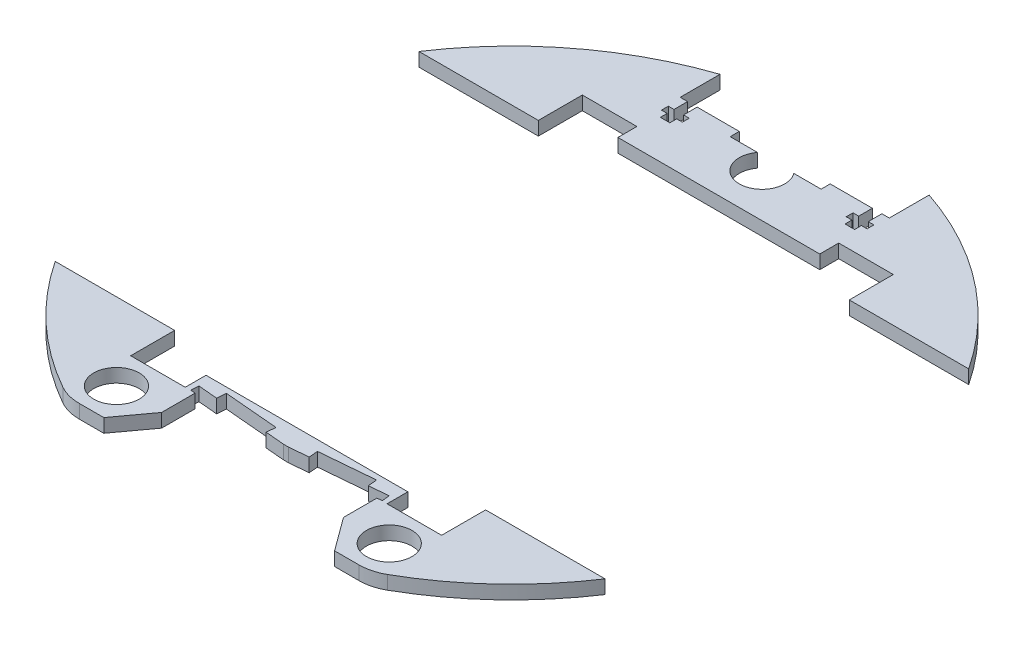
SolidWorks part; units mm, degrees
ref_plane "Front Plane" through (0, 0, 0) normal (0, 0, 1) x (1, 0, 0)
ref_plane "Top Plane" through (0, 0, 0) normal (0, 1, 0) x (1, 0, 0)
ref_plane "Right Plane" through (0, 0, 0) normal (1, 0, 0) x (0, 0, -1)
sketch "Sketch1" plane through (0, 0, 0) normal (0, 1, 0) x (1, 0, 0)
  line L0 (-30.7634, -64.4046) -> (30.7634, -64.4046)
  line L1 (0, -83.2398) -> (0, 0) construction
  line L2 (0, -83.2398) -> (33.2911, -64.4046) construction
  arc A0 (35.6856, -63.1093) -> (-35.6856, -63.1093) centre (0, 0) ccw
  circle A1 centre (0, -83.2398) radius 38.25 construction
  arc A2 (30.7634, -64.4046) -> (35.6856, -63.1093) centre (30.7634, -54.4046) ccw
  arc A3 (-30.7634, -64.4046) -> (-35.6856, -63.1093) centre (-30.7634, -54.4046) cw
  dimension "D1" = 145
  dimension "D2" = 76.5
  dimension "D4" = 10
  dimension "D3" = 60.5
extrude "Boss-Extrude1" add sketch "Sketch1" along normal blind 3
sketch "Sketch2" plane through (0, 3, 0) normal (0, 1, 0) x (1, 0, 0)
  line L5 (22.2, -49.6757) -> (22.2, -45.1)
  line L6 (22.2, -45.1) -> (-22.2, -45.1)
  line L7 (-22.2, -45.1) -> (-22.2, -49.6757)
  line L8 (22.2, 49.6757) -> (22.2, 45.5)
  line L9 (-34.2, -49.6757) -> (-22.2, -49.6757) construction
  line L10 (-34.2, -49.6757) -> (-34.2, 49.6757) construction
  line L11 (-34.2, 49.6757) -> (-22.2, 49.6757) construction
  line L19 (34.2, 49.6757) -> (22.2, 49.6757) construction
  line L20 (34.2, -49.6757) -> (34.2, 49.6757) construction
  line L21 (34.2, -49.6757) -> (22.2, -49.6757) construction
  line L22 (22.2, 45.5) -> (-22.2, 45.5)
  line L23 (-22.2, 45.5) -> (-22.2, 49.6757)
  line L35 (-34.2, -49.6757) -> (-22.2, -49.6757)
  line L36 (-34.2, -49.6757) -> (-34.2, 49.6757)
  line L37 (-34.2, 49.6757) -> (-22.2, 49.6757)
  line L55 (34.2, 49.6757) -> (22.2, 49.6757)
  line L56 (34.2, -49.6757) -> (34.2, 49.6757)
  line L57 (34.2, -49.6757) -> (22.2, -49.6757)
  dimension "D1" = 45.1
  dimension "D2" = 45.5
extrude "Cut-Extrude1" cut sketch "Sketch2" against normal through all contours L55 L37 L36 L35 L7 L6 L5 L57 L56 region at (0, 3, -0.1256)
sketch "Sketch3" plane through (0, 3, 0) normal (0, 1, 0) x (1, 0, 0)
  line L0 (-34.2, 40) -> (-34.2, -40)
  line L1 (-72.5, -40) -> (-34.2, -40)
  line L2 (-72.5, -40) -> (-72.5, 40)
  line L3 (-72.5, 40) -> (-34.2, 40)
  line L4 (72.5, -40) -> (72.5, 40)
  line L5 (-72.5, -40) -> (72.5, 40) construction
  line L6 (-72.5, 40) -> (72.5, -40) construction
  line L7 (-34.2, -49.6757) -> (-34.2, 49.6757) construction
  line L8 (34.2, 40) -> (34.2, -40)
  line L9 (34.2, -49.6757) -> (34.2, 49.6757) construction
  line L10 (34.2, 40) -> (72.5, 40)
  line L11 (34.2, -40) -> (72.5, -40)
  arc A0 (35.6856, -63.1093) -> (-35.6856, -63.1093) centre (0, 0) ccw construction
  point P0 (0, 0)
  dimension "D1" = 80
extrude "Cut-Extrude2" cut sketch "Sketch3" against normal through all
sketch "Sketch4" plane through (0, 3, 0) normal (0, 1, 0) x (1, 0, 0)
  line L0 (-21.0702, -49.6179) -> (-0.6482, -51.4046)
  line L1 (21.0702, -49.6179) -> (20.922, -47.9244)
  line L2 (0.6482, -51.4046) -> (0.5, -49.7111)
  line L3 (20.922, -47.9244) -> (0.5, -49.7111)
  line L4 (0, 0) -> (0, -64.4046) construction
  line L5 (-30.7634, -64.4046) -> (30.7634, -64.4046) construction
  line L6 (-20.922, -47.9244) -> (-0.5, -49.7111)
  line L7 (-0.6482, -51.4046) -> (-0.5, -49.7111)
  line L8 (-21.0702, -49.6179) -> (-20.922, -47.9244)
  line L14 (21.0702, -49.6179) -> (0.6482, -51.4046)
  dimension "D1" = 1.7
  dimension "D2" = 20.5
  dimension "D3" = 5
  dimension "D4" = 13
  dimension "D5" = 0.5
extrude "Cut-Extrude3" cut sketch "Sketch4" against normal through all
sketch "Sketch5" plane through (0, 3, 0) normal (0, 1, 0) x (1, 0, 0)
  line L0 (-20, -64.4046) -> (-20, -49.7115)
  line L4 (0.6482, -51.4046) -> (21.0702, -49.6179) construction
  line L5 (16.6882, -48.2948) -> (4.7338, -49.3407)
  line L6 (16.6882, -48.2948) -> (16.5139, -46.3024)
  line L7 (4.7338, -49.3407) -> (4.5595, -47.3483)
  line L8 (16.5139, -46.3024) -> (4.5595, -47.3483)
  line L9 (20.922, -47.9244) -> (0.5, -49.7111) construction
  line L10 (0, 0) -> (0, -49.7115) construction
  line L11 (20, -64.4046) -> (20, -49.7115)
  line L13 (-16.5139, -46.3024) -> (-4.5595, -47.3483)
  line L14 (-4.7338, -49.3407) -> (-4.5595, -47.3483)
  line L15 (-16.6882, -48.2948) -> (-16.5139, -46.3024)
  line L16 (-16.6882, -48.2948) -> (-4.7338, -49.3407)
  line L22 (-30.7634, -64.4046) -> (30.7634, -64.4046) construction
  line L23 (20, -49.7115) -> (-20, -49.7115)
  line L25 (-20, -64.4046) -> (20, -64.4046)
  point P14 (10.711, -48.8177)
  point P15 (10.711, -48.8177)
  dimension "D1" = 12
  dimension "D2" = 40
  dimension "D4" = 2
extrude "Cut-Extrude4" cut sketch "Sketch5" against normal through all
sketch "Sketch6" plane through (0, 3, 0) normal (0, 1, 0) x (1, 0, 0)
  line L0 (0, 0) -> (0, 60) construction
  line L1 (-23, 72.5) -> (23, 72.5)
  line L2 (-23, 72.5) -> (-23, 60)
  line L3 (-23, 60) -> (-10, 60)
  line L4 (23, 72.5) -> (23, 60)
  line L5 (10, 60) -> (23, 60)
  line L7 (10, 60) -> (10, 58)
  line L8 (10, 58) -> (-10, 58)
  line L9 (-10, 60) -> (-10, 58)
  arc A1 (60.4669, 40) -> (-60.4669, 40) centre (0, 0) ccw construction
  point P14 (0, 58)
  dimension "D1" = 20
  dimension "D2" = 46
  dimension "D3" = 60
  dimension "D4" = 2
extrude "Cut-Extrude5" cut sketch "Sketch6" against normal through all
sketch "Sketch7" plane through (0, 3, 0) normal (0, 1, 0) x (1, 0, 0)
  line L0 (0, 0) -> (0, -31.2827) construction
  circle A0 centre (-30, -57) radius 5
  circle A4 centre (30, -57) radius 5
  dimension "D1" = 10
  dimension "D2" = 30
  dimension "D3" = 57
extrude "Cut-Extrude6" cut sketch "Sketch7" against normal through all
sketch "Sketch9" plane through (0, 3, 0) normal (0, 1, 0) x (1, 0, 0)
  line L0 (-23, 60) -> (-10, 60) construction
  line L1 (22.62, 57) -> (18.02, 57)
  line L2 (22.62, 57) -> (22.62, 55.5)
  line L3 (22.62, 55.5) -> (18.02, 55.5)
  line L4 (18.02, 57) -> (18.02, 55.5)
  line L5 (0, 0) -> (0, 44) construction
  line L7 (-18.02, 57) -> (-18.02, 55.5)
  line L8 (-22.62, 55.5) -> (-18.02, 55.5)
  line L9 (-22.62, 57) -> (-22.62, 55.5)
  line L10 (-22.62, 57) -> (-18.02, 57)
  point P4 (20.32, 55.5)
  dimension "D1" = 20.32
  dimension "D2" = 1.5
  dimension "D3" = 4.6
  dimension "D4" = 3
extrude "Cut-Extrude8" cut sketch "Sketch9" against normal through all
sketch "Sketch10" plane through (0, 3, 0) normal (0, 1, 0) x (1, 0, 0)
  line L0 (22.62, 57) -> (18.02, 57) construction
  line L1 (21.37, 57) -> (19.27, 57)
  line L2 (21.37, 57) -> (21.37, 60)
  line L3 (21.37, 60) -> (19.27, 60)
  line L4 (19.27, 57) -> (19.27, 60)
  line L5 (-23, 60) -> (-10, 60) construction
  line L6 (0, 0) -> (0, 44) construction
  line L8 (18.02, 55.5) -> (22.62, 55.5) construction
  line L9 (21.37, 55.5) -> (19.27, 55.5)
  line L10 (21.37, 55.5) -> (21.37, 54)
  line L11 (21.37, 54) -> (19.27, 54)
  line L12 (19.27, 55.5) -> (19.27, 54)
  line L13 (-19.27, 55.5) -> (-19.27, 54)
  line L14 (-21.37, 54) -> (-19.27, 54)
  line L15 (-21.37, 55.5) -> (-21.37, 54)
  line L16 (-21.37, 55.5) -> (-19.27, 55.5)
  line L17 (-19.27, 57) -> (-19.27, 60)
  line L18 (-21.37, 60) -> (-19.27, 60)
  line L19 (-21.37, 57) -> (-21.37, 60)
  line L20 (-21.37, 57) -> (-19.27, 57)
  point P14 (20.32, 57)
  point P16 (20.32, 57)
  dimension "D1" = 2.1
  dimension "D2" = 6
extrude "Cut-Extrude9" cut sketch "Sketch10" against normal through all
sketch "Sketch11" plane through (0, 3, 0) normal (0, 1, 0) x (1, 0, 0)
  line L0 (0, 0) -> (0, 55) construction
  circle A0 centre (0, 55) radius 5
  dimension "D2" = 10
  dimension "D1" = 55
extrude "Cut-Extrude10" cut sketch "Sketch11" against normal through all
sketch "Sketch13" plane through (0, 3, 0) normal (0, 1, 0) x (1, 0, 0)
  line L0 (20, -57.0581) -> (25.3817, -64.4046)
  line L1 (20, -64.4046) -> (20, -49.7115) construction
  line L2 (20, -64.4046) -> (30.7634, -64.4046) construction
  line L3 (25.3817, -64.4046) -> (20, -64.4046)
  line L4 (20, -64.4046) -> (20, -57.0581)
  line L5 (0, 0) -> (0, -25.0729) construction
  line L6 (-20, -64.4046) -> (-20, -57.0581)
  line L7 (-25.3817, -64.4046) -> (-20, -64.4046)
  line L8 (-20, -57.0581) -> (-25.3817, -64.4046)
extrude "Cut-Extrude11" cut sketch "Sketch13" against normal through all
equation "\"smallPulleyTeeth\"= 30"
equation "\"largePulleyTeeth\"= 30"
equation "\"eighthThick\"= 3.0mm"
equation "\"sixteenthThick\"= 1.7mm"
equation "\"quarterThick\"=6.0mm"
equation "\"OD\"= 145mm"
equation "\"puckAngle\"= 60.5deg"
equation "\"puckDiam\"= 76.5mm"
equation "\"axlePress\"= 5.9mm"
equation "\"press\"= 0.2mm"
equation "\"wheelClear\"= 0.3mm"
equation "\"10-32clear\"= 4.8mm"
equation "\"6-32clear\"= 3.3mm"
equation "\"8-32clear\"= 4.0mm"
equation "\"4-40clear\"= 3.0mm"
equation "\"wheelHeight\"= 22mm"
equation "\"wheelWell\"= 65mm"
equation "\"D1@Sketch1\"=\"OD\""
equation "\"D1@Boss-Extrude1\"=\"eighthThick\""
equation "\"D2@Sketch1\"=\"puckDiam\""
equation "\"D3@Sketch1\"=\"puckAngle\""
